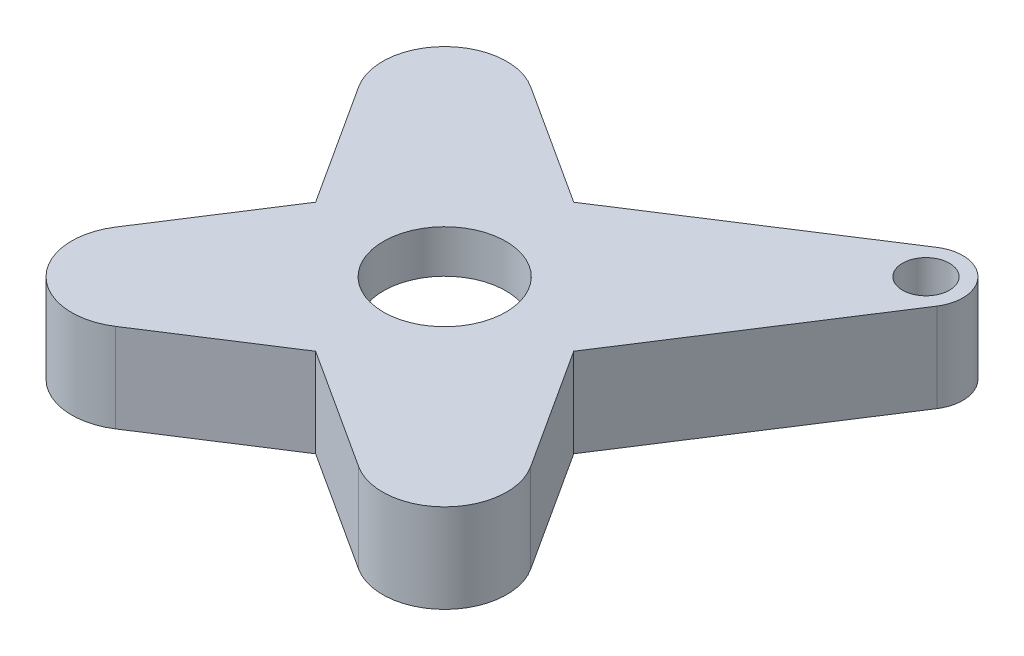
SolidWorks part; units mm, degrees
ref_plane "Front Plane" through (0, 0, 0) normal (0, 0, 1) x (1, 0, 0)
ref_plane "Top Plane" through (0, 0, 0) normal (0, 1, 0) x (1, 0, 0)
ref_plane "Right Plane" through (0, 0, 0) normal (1, 0, 0) x (0, 0, -1)
sketch "Sketch1" plane through (0, 0, 0) normal (0, 1, 0) x (1, 0, 0)
  line L0 (-13.0815, -13.0815) -> (13.0815, 13.0815) construction
  line L1 (-13.0815, 13.0815) -> (13.0815, -13.0815) construction
  line L2 (7.57, 1.4889) -> (13.3608, 10.4574)
  line L3 (1.4889, 7.57) -> (10.4574, 13.3608)
  line L4 (7.57, 1.4889) -> (1.4889, 7.57) construction
  line L5 (13.3608, -10.4574) -> (7.57, -1.4889)
  line L6 (10.4574, -13.3608) -> (1.4889, -7.57)
  line L7 (-13.3608, -10.4574) -> (-7.57, -1.4889)
  line L8 (-10.4574, -13.3608) -> (-1.4889, -7.57)
  line L9 (-10.4574, 13.3608) -> (-1.4889, 7.57)
  line L10 (-7.57, 1.4889) -> (-13.3608, 10.4574)
  line L11 (8.0238, 1.0211) -> (13.8942, 10.113)
  line L12 (1.0211, 8.0238) -> (10.113, 13.8942)
  line L13 (-10.113, 13.8942) -> (-1.0211, 8.0238)
  line L14 (-8.0238, 1.0211) -> (-13.8942, 10.113)
  line L15 (-13.8942, -10.113) -> (-8.0238, -1.0211)
  line L16 (-10.113, -13.8942) -> (-1.0211, -8.0238)
  line L17 (10.113, -13.8942) -> (1.0211, -8.0238)
  line L18 (13.8942, -10.113) -> (8.0238, -1.0211)
  line L19 (9.6321, 0) -> (15.4946, 9.0797)
  line L20 (0, 9.6321) -> (9.0797, 15.4946)
  line L21 (-9.0797, 15.4946) -> (0, 9.6321)
  line L22 (-9.6321, 0) -> (-15.4946, 9.0797)
  line L23 (-15.4946, -9.0797) -> (-9.6321, 0)
  line L24 (-9.0797, -15.4946) -> (0, -9.6321)
  line L25 (9.0797, -15.4946) -> (0, -9.6321)
  line L26 (15.4946, -9.0797) -> (9.6321, 0)
  line L27 (15.4946, 9.0797) -> (20.2671, 16.4712)
  line L28 (9.0797, 15.4946) -> (16.4712, 20.2671)
  circle A0 centre (0, 0) radius 6.7736 construction
  arc A1 (10.4574, 13.3608) -> (13.3608, 10.4574) centre (11.5966, 11.5966) cw
  arc A2 (-1.4889, 7.57) -> (1.4889, 7.57) centre (0, 8.5636) ccw
  arc A3 (7.57, 1.4889) -> (7.57, -1.4889) centre (8.5636, 0) ccw
  arc A4 (-1.4889, -7.57) -> (1.4889, -7.57) centre (0, -8.5636) cw
  arc A5 (13.3608, -10.4574) -> (10.4574, -13.3608) centre (11.5966, -11.5966) cw
  arc A6 (-7.57, 1.4889) -> (-7.57, -1.4889) centre (-8.5636, 0) cw
  arc A7 (-13.3608, -10.4574) -> (-10.4574, -13.3608) centre (-11.5966, -11.5966) ccw
  arc A8 (-13.3608, 10.4574) -> (-10.4574, 13.3608) centre (-11.5966, 11.5966) cw
  arc A11 (10.113, 13.8942) -> (13.8942, 10.113) centre (11.5966, 11.5966) cw
  arc A12 (-1.0211, 8.0238) -> (1.0211, 8.0238) centre (0, 8.5636) ccw
  arc A13 (-13.8942, 10.113) -> (-10.113, 13.8942) centre (-11.5966, 11.5966) cw
  arc A14 (-8.0238, 1.0211) -> (-8.0238, -1.0211) centre (-8.5636, 0) cw
  arc A15 (-13.8942, -10.113) -> (-10.113, -13.8942) centre (-11.5966, -11.5966) ccw
  arc A16 (-1.0211, -8.0238) -> (1.0211, -8.0238) centre (0, -8.5636) cw
  arc A17 (13.8942, -10.113) -> (10.113, -13.8942) centre (11.5966, -11.5966) cw
  arc A18 (8.0238, 1.0211) -> (8.0238, -1.0211) centre (8.5636, 0) ccw
  arc A20 (0, 9.6321) -> (0, 9.6321) centre (0, 9.6321) ccw
  arc A21 (-15.4946, 9.0797) -> (-9.0797, 15.4946) centre (-11.5966, 11.5966) cw
  arc A22 (-9.6321, 0) -> (-9.6321, 0) centre (-9.6321, 0) cw
  arc A23 (-15.4946, -9.0797) -> (-9.0797, -15.4946) centre (-11.5966, -11.5966) ccw
  arc A24 (0, -9.6321) -> (0, -9.6321) centre (0, -9.6321) cw
  arc A25 (15.4946, -9.0797) -> (9.0797, -15.4946) centre (11.5966, -11.5966) cw
  arc A26 (9.6321, 0) -> (9.6321, 0) centre (9.6321, 0) ccw
  arc A27 (9.0797, 15.4946) -> (15.4946, 9.0797) centre (11.5966, 11.5966) cw construction
  arc A28 (16.4712, 20.2671) -> (20.2671, 16.4712) centre (17.9605, 17.9605) cw
  circle A29 centre (17.9605, 17.9605) radius 1.75
  circle A30 centre (0, 0) radius 4.572
  point P5 (0, 0)
  point P8 (0, 0)
  point P31 (4.5294, 4.5294)
  point P66 (0, 0)
  dimension "D2" = 2.1
  dimension "D3" = 1.79
  dimension "D6" = 0.635
  dimension "D8" = 25.4
  dimension "4.5mm" = 3.5
  dimension "D9" = 9.144
  dimension "D1" = 18.5
  dimension "D4" = 7.57
  dimension "D5" = 8.6
  dimension "D7" = 2.54
extrude "Boss-Extrude1" add sketch "Sketch1" along normal blind 3.2004 contours A28 L28 L20 L21 A21 L22 L23 A23 L24 L25 A25 L26 L19 L27 A29 L11 A18 L18 A17 L17 A16 L16 A15 L15 A14 L14 A13 L13 A12 L12 A11 | A8 L10 A6 L7 A7 L8 A4 L6 A5 L5 A3 L2 A1 L3 A2 L9 | A18 L11 A11 L12 A12 L13 A13 L14 A14 L15 A15 L16 A16 L17 A17 L18 L10 A8 L9 A2 L3 A1 L2 A3 L5 A5 L6 A4 L8 A7 L7 A6 region at (6.3862, 0, 0) region at (7.0033, 0, 0) region at (12.1245, 0, 4.8232)
extrude "Boss-Extrude2" add sketch "Sketch1<3>" against normal blind 3.429 contours A28 L28 L20 L21 A21 L22 L23 A23 L24 L25 A25 L26 L19 L27 A29 L11 A18 L18 A17 L17 A16 L16 A15 L15 A14 L14 A13 L13 A12 L12 A11 | A18 L11 A11 L12 A12 L13 A13 L14 A14 L15 A15 L16 A16 L17 A17 L18 L10 A8 L9 A2 L3 A1 L2 A3 L5 A5 L6 A4 L8 A7 L7 A6 region at (7.0033, 0, 0) region at (12.1245, 0, 4.8232)
sketch "Sketch1<3>" plane through (0, 0, 0) normal (0, 1, 0) x (1, 0, 0) same geometry as "Sketch1"
